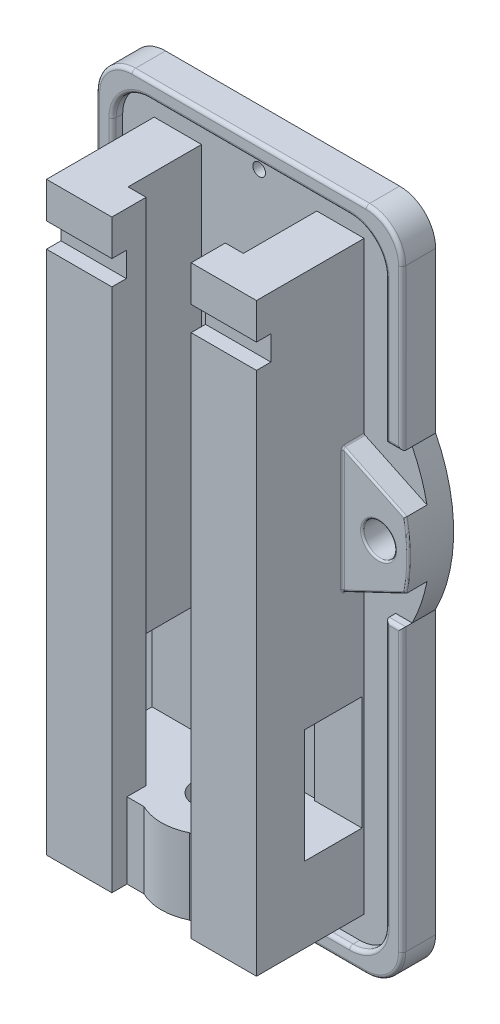
SolidWorks part; units mm, degrees
ref_plane "Front Plane" through (0, 0, 0) normal (0, 0, 1) x (1, 0, 0)
ref_plane "Top Plane" through (0, 0, 0) normal (0, 1, 0) x (1, 0, 0)
ref_plane "Right Plane" through (0, 0, 0) normal (1, 0, 0) x (0, 0, -1)
sketch "Sketch1" plane through (0, 0, 0) normal (0, 0, 1) x (1, 0, 0)
  line L1 (-53.975, 117.475) -> (53.975, 117.475)
  line L2 (-53.975, 117.475) -> (-53.975, -117.475)
  line L3 (-53.975, -117.475) -> (53.975, -117.475)
  line L4 (53.975, 117.475) -> (53.975, -117.475)
  line L5 (-53.975, 117.475) -> (53.975, -117.475) construction
  line L6 (-53.975, -117.475) -> (53.975, 117.475) construction
  circle A0 centre (0, 21.463) radius 7.112
  circle A1 centre (0, 106.045) radius 2.2225
  point P0 (0, 0)
  point P8 (0, 28.575)
  dimension "D3" = 14.224
  dimension "D5" = 11.43
  dimension "D1" = 234.95
  dimension "D2" = 107.95
  dimension "D4" = 88.9
extrude "Boss-Extrude1" add sketch "Sketch1" along normal blind 8.255
sketch "Sketch7" plane through (0, 0, 0) normal (0, 0, 1) x (1, 0, 0)
  circle A0 centre (0, 21.463) radius 7.112
  circle A1 centre (0, 21.463) radius 60.325
extrude "Boss-Extrude3" add sketch "Sketch7" along normal up to surface (8.255 mm away) up to face at (7.112, 21.463, 8.255)
sketch "Sketch2" plane through (0, 0, 8.255) normal (0, 0, 1) x (1, 0, 0)
  line L0 (53.975, 117.475) -> (-53.975, 117.475) construction
  line L1 (-37.0205, 103.505) -> (37.0205, 103.505)
  line L2 (-37.0205, 103.505) -> (-37.0205, -102.87)
  line L3 (-37.0205, -102.87) -> (37.0205, -102.87)
  line L4 (37.0205, 103.505) -> (37.0205, -102.87)
  line L5 (-37.0205, 103.505) -> (37.0205, -102.87) construction
  line L6 (-37.0205, -102.87) -> (37.0205, 103.505) construction
  point P0 (0, 0.3175)
  dimension "D1" = 206.375
  dimension "D2" = 74.041
  dimension "D3" = 13.97
extrude "Boss-Extrude2" add sketch "Sketch2" along normal blind 37.973
sketch "Sketch3" plane through (0, 103.505, 0) normal (0, 1, 0) x (1, 0, 0)
  line L0 (-13.97, -46.228) -> (13.97, -46.228)
  line L1 (37.0205, -46.228) -> (-37.0205, -46.228) construction
  line L2 (-20.32, -8.255) -> (20.32, -8.255)
  line L4 (37.0205, -8.255) -> (-37.0205, -8.255) construction
  line L5 (-20.32, -8.255) -> (-20.32, -34.163)
  line L6 (-20.32, -34.163) -> (-13.97, -34.163)
  line L7 (-13.97, -34.163) -> (-13.97, -46.228)
  line L8 (20.32, -8.255) -> (20.32, -34.163)
  line L9 (20.32, -34.163) -> (13.97, -34.163)
  line L10 (13.97, -34.163) -> (13.97, -46.228)
  point P5 (0, -46.228)
  point P8 (0, -8.255)
  dimension "D1" = 40.64
  dimension "D2" = 27.94
  dimension "D3" = 12.065
extrude "Cut-Extrude1" cut sketch "Sketch3" against normal offset from surface (179.705 mm away) 26.67 up to face at (0, -102.87, 27.2415)
sketch "Sketch4" plane through (0, -102.87, 0) normal (0, -1, 0) x (1, 0, 0)
  line L0 (0, 43.9691) -> (0, 9.1483) construction
  line L1 (-13.97, 46.228) -> (-13.97, 40.894)
  line L2 (-13.97, 46.228) -> (-13.97, 34.163) construction
  line L3 (-13.97, 40.894) -> (-8.001, 40.894)
  line L4 (-13.97, 46.228) -> (13.97, 46.228)
  line L5 (13.97, 40.894) -> (8.001, 40.894)
  line L6 (13.97, 46.228) -> (13.97, 40.894)
  circle A0 centre (0, 24.511) radius 6.985
  arc A1 (8.001, 40.894) -> (-8.001, 40.894) centre (0, 24.511) ccw
  dimension "D3" = 13.97
  dimension "D1" = 5.334
  dimension "D2" = 8.001
extrude "Cut-Extrude2" cut sketch "Sketch4" against normal through all
sketch "Sketch5" plane through (-37.0205, 0, 0) normal (-1, 0, 0) x (0, 0, 1)
  line L0 (46.228, 103.505) -> (46.228, -102.87) construction
  line L1 (46.228, 90.805) -> (41.148, 90.805)
  line L2 (46.228, 90.805) -> (46.228, 82.169)
  line L3 (46.228, 82.169) -> (41.148, 82.169)
  line L4 (41.148, 90.805) -> (41.148, 82.169)
  line L5 (46.228, 103.505) -> (8.255, 103.505) construction
  line L7 (9.0237, -76.2) -> (29.21, -76.2)
  line L8 (9.0237, -76.2) -> (9.0237, -36.068)
  line L9 (9.0237, -36.068) -> (29.21, -36.068)
  line L10 (29.21, -76.2) -> (29.21, -36.068)
  line L12 (34.163, -76.2) -> (8.255, -76.2) construction
  line L13 (8.255, 117.475) -> (8.255, 48.4038) construction
  dimension "D1" = 12.7
  dimension "D2" = 8.636
  dimension "D3" = 5.08
  dimension "D4" = 40.132
  dimension "D5" = 20.955
extrude "Cut-Extrude3" cut sketch "Sketch5" against normal through all
sketch "Sketch8" plane through (0, 0, 8.255) normal (0, 0, 1) x (1, 0, 0)
  line L0 (-37.0205, 43.688) -> (-37.0205, -0.762)
  line L1 (-37.0205, 82.169) -> (-37.0205, -102.87) construction
  line L2 (-2.6168, 21.463) -> (5.5666, 21.463) construction
  line L3 (0, 27.2792) -> (0, 17.3783) construction
  line L4 (-59.1827, 9.779) -> (-37.0205, -0.762)
  line L5 (-59.1827, 33.147) -> (-37.0205, 43.688)
  line L6 (59.1827, 33.147) -> (37.0205, 43.688)
  line L7 (59.1827, 9.779) -> (37.0205, -0.762)
  line L8 (37.0205, 43.688) -> (37.0205, -0.762)
  arc A0 (-53.975, 48.4038) -> (-53.975, -5.4778) centre (0, 21.463) ccw construction
  arc A1 (-59.1827, 33.147) -> (-59.1827, 9.779) centre (0, 21.463) ccw
  arc A2 (59.1827, 33.147) -> (59.1827, 9.779) centre (0, 21.463) cw
  point P0 (-60.325, 21.463)
  point P5 (-37.0205, 21.463)
  point P21 (37.0205, 21.463)
  dimension "D1" = 44.45
  dimension "D2" = 11.684
extrude "Boss-Extrude4" add sketch "Sketch8" along normal blind 7.62
sketch "Sketch9" plane through (0, 0, 15.875) normal (0, 0, 1) x (1, 0, 0)
  line L0 (-37.0205, 82.169) -> (-37.0205, -102.87) construction
  line L1 (0, 67.7284) -> (0, -11.6845) construction
  circle A0 centre (-49.7205, 21.463) radius 5.715
  arc A1 (-59.1827, 33.147) -> (-59.1827, 9.779) centre (0, 21.463) ccw construction
  circle A2 centre (49.7205, 21.463) radius 5.715
  point P6 (-60.325, 21.463)
  point P7 (-44.0055, 21.463)
  point P14 (44.0055, 21.463)
  dimension "D1" = 11.43
  dimension "D2" = 6.985
extrude "Cut-Extrude4" cut sketch "Sketch9" against normal through all
sketch "Sketch10" plane through (0, 0, 8.255) normal (0, 0, 1) x (1, 0, 0)
  line L0 (-53.975, 48.4038) -> (-53.975, 117.475)
  line L1 (-53.975, 117.475) -> (53.975, 117.475)
  line L2 (53.975, 117.475) -> (53.975, 48.4038)
  line L3 (53.975, 48.4038) -> (48.133, 48.4038)
  line L4 (48.133, 48.4038) -> (48.133, 111.633)
  line L5 (48.133, 111.633) -> (-48.133, 111.633)
  line L6 (-48.133, 111.633) -> (-48.133, 48.4038)
  line L7 (-48.133, 48.4038) -> (-53.975, 48.4038)
  line L8 (-53.975, -5.4778) -> (-53.975, -117.475)
  line L9 (-53.975, -117.475) -> (53.975, -117.475)
  line L10 (53.975, -117.475) -> (53.975, -5.4778)
  line L11 (53.975, -5.4778) -> (48.133, -5.4778)
  line L12 (48.133, -5.4778) -> (48.133, -111.633)
  line L13 (48.133, -111.633) -> (-48.133, -111.633)
  line L14 (-48.133, -111.633) -> (-48.133, -5.4778)
  line L15 (-48.133, -5.4778) -> (-53.975, -5.4778)
  dimension "D1" = 5.842
  dimension "D2" = 5.842
extrude "Boss-Extrude5" add sketch "Sketch10" along normal blind 3.556
fillet "Fillet1" radius 12.7 8 edges at (53.975, 117.475, 5.9055) (48.133, 111.633, 10.033) (-48.133, 111.633, 10.033) (48.133, -111.633, 10.033) (-48.133, -111.633, 10.033) (-53.975, 117.475, 5.9055) (53.975, -117.475, 5.9055) (-53.975, -117.475, 5.9055)
fillet "Fillet2" radius 1.27 24 edges at (-50.2553, -113.7553, 11.811) (-53.975, -55.1264, 11.811) (-51.054, -5.4778, 11.811) (-48.133, -52.2054, 11.811) (-44.4133, -107.9133, 11.811) (0, -111.633, 11.811) (44.4133, -107.9133, 11.811) (48.133, -52.2054, 11.811) (51.054, -5.4778, 11.811) (53.975, -55.1264, 11.811) (50.2553, -113.7553, 11.811) (0, -117.475, 11.811) (51.054, 48.4038, 11.811) (48.133, 73.6684, 11.811) (44.4133, 107.9133, 11.811) (0, 111.633, 11.811) (-44.4133, 107.9133, 11.811) (-48.133, 73.6684, 11.811) (-51.054, 48.4038, 11.811) (-53.975, 76.5894, 11.811) (-50.2553, 113.7553, 11.811) (0, 117.475, 11.811) (50.2553, 113.7553, 11.811) (53.975, 76.5894, 11.811)
fillet "Fillet3" radius 0.635 14 edges at (37.0205, -0.762, 12.065) (37.0205, 43.688, 12.065) (-37.0205, 43.688, 12.065) (-37.0205, -0.762, 12.065) (48.1016, 4.5085, 15.875) (37.0205, 21.463, 15.875) (48.1016, 38.4175, 15.875) (60.325, 21.463, 15.875) (44.0055, 21.463, 15.875) (-60.325, 21.463, 15.875) (-48.1016, 38.4175, 15.875) (-37.0205, 21.463, 15.875) (-48.1016, 4.5085, 15.875) (-44.0055, 21.463, 15.875)
equation "\"1.31.495in\"=1.495"
